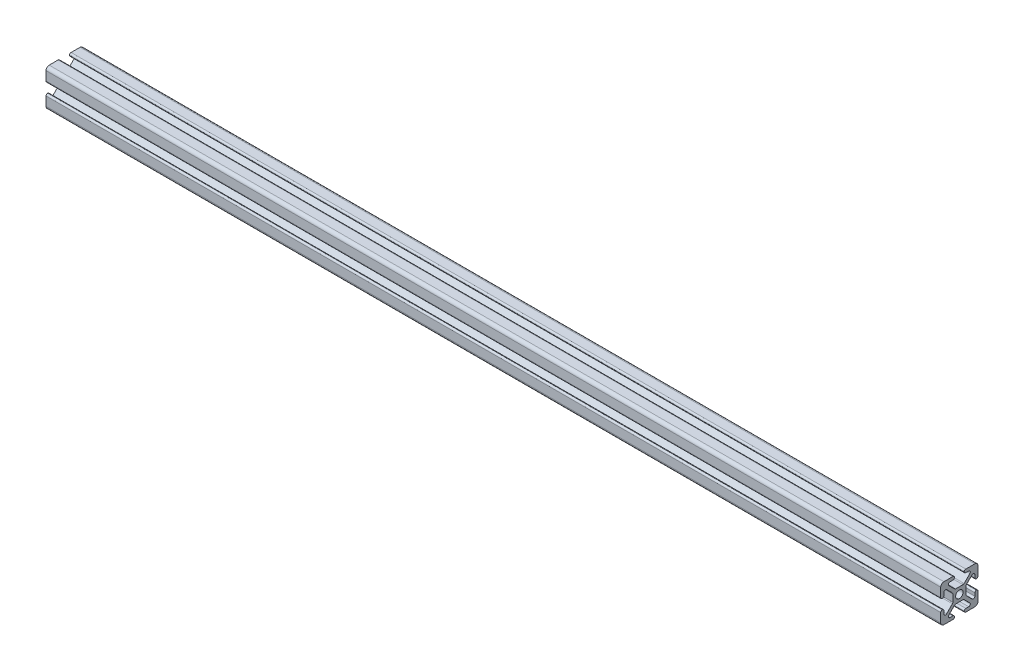
SolidWorks part; units mm, degrees
ref_plane "Front Plane" through (0, 0, 0) normal (1, 0, 0) x (0, 1, 0)
ref_plane "Top Plane" through (0, 0, 0) normal (0, 0, 1) x (0, 1, 0)
ref_plane "Right Plane" through (0, 0, 0) normal (0, 1, 0) x (-1, 0, 0)
sketch "Sketch1" plane through (0, 0, 0) normal (1, 0, 0) x (0, 1, 0)
  line L0 (0, 0) -> (0, 12.5) construction
  line L1 (-12.5, -12.5) -> (12.5, -12.5)
  line L2 (-12.5, -12.5) -> (-12.5, 12.5)
  line L3 (-12.5, 12.5) -> (12.5, 12.5)
  line L4 (12.5, -12.5) -> (12.5, 12.5)
  line L5 (-12.5, -12.5) -> (12.5, 12.5) construction
  line L6 (-12.5, 12.5) -> (12.5, -12.5) construction
  line L7 (-3.25, 12.5) -> (-3.25, 10.37)
  line L8 (-3.25, 10.37) -> (-8.8639, 10.37)
  line L9 (-8.8639, 10.37) -> (-2.8739, 4.38)
  line L10 (-2.8739, 4.38) -> (2.8739, 4.38)
  line L11 (8.8639, 10.37) -> (2.8739, 4.38)
  line L12 (3.25, 10.37) -> (8.8639, 10.37)
  line L13 (3.25, 12.5) -> (3.25, 10.37)
  line L14 (12.5, -3.25) -> (10.37, -3.25)
  line L15 (10.37, -3.25) -> (10.37, -8.8639)
  line L16 (10.37, -8.8639) -> (4.38, -2.8739)
  line L17 (4.38, 2.8739) -> (4.38, -2.8739)
  line L18 (10.37, 8.8639) -> (4.38, 2.8739)
  line L19 (10.37, 3.25) -> (10.37, 8.8639)
  line L20 (12.5, 3.25) -> (10.37, 3.25)
  line L21 (-3.25, -12.5) -> (-3.25, -10.37)
  line L22 (-3.25, -10.37) -> (-8.8639, -10.37)
  line L23 (-8.8639, -10.37) -> (-2.8739, -4.38)
  line L24 (2.8739, -4.38) -> (-2.8739, -4.38)
  line L25 (8.8639, -10.37) -> (2.8739, -4.38)
  line L26 (3.25, -10.37) -> (8.8639, -10.37)
  line L27 (3.25, -12.5) -> (3.25, -10.37)
  line L28 (-12.5, 3.25) -> (-10.37, 3.25)
  line L29 (-10.37, 3.25) -> (-10.37, 8.8639)
  line L30 (-10.37, 8.8639) -> (-4.38, 2.8739)
  line L31 (-4.38, -2.8739) -> (-4.38, 2.8739)
  line L32 (-10.37, -8.8639) -> (-4.38, -2.8739)
  line L33 (-10.37, -3.25) -> (-10.37, -8.8639)
  line L34 (-12.5, -3.25) -> (-10.37, -3.25)
  circle A0 centre (0, 0) radius 2.5
  point P0 (0, 0)
  point P15 (0, 4.38)
  dimension "D3" = 5
  dimension "D1" = 25
  dimension "D2" = 25
  dimension "D4" = 2.13
  dimension "D5" = 2.13
  dimension "D6" = 6.5
  dimension "D7" = 4.38
  dimension "D8" = 4
extrude "Boss-Extrude1" add sketch "Sketch1" along normal blind 600 contours L34 L2 L1 L21 L22 L23 L24 L25 L26 L27 L4 L14 L15 L16 L17 L18 L19 L20 L3 L13 L12 L11 L10 L9 L8 L7 L28 L29 L30 L31 L32 L33 A0 region at (0, -12.1464, -7.875)
fillet "Fillet1" radius 1.065 32 edges at (300, -10.37, -8.8639) (300, 2.8739, -4.38) (300, -2.8739, -4.38) (300, -4.38, 2.8739) (300, -4.38, -2.8739) (300, -2.8739, 4.38) (300, 2.8739, 4.38) (300, 4.38, 2.8739) (300, 4.38, -2.8739) (300, -8.8639, -10.37) (300, 8.8639, -10.37) (300, 10.37, -8.8639) (300, -10.37, 8.8639) (300, -8.8639, 10.37) (300, 10.37, 8.8639) (300, 8.8639, 10.37) (300, 12.5, 3.25) (300, -3.25, -12.5) (300, -10.37, 3.25) (300, 10.37, 3.25) (300, -10.37, -3.25) (300, -12.5, -3.25) (300, -12.5, 3.25) (300, 3.25, -10.37) (300, -3.25, -10.37) (300, 3.25, -12.5) (300, 10.37, -3.25) (300, 12.5, -3.25) (300, 3.25, 12.5) (300, 3.25, 10.37) (300, -3.25, 10.37) (300, -3.25, 12.5)
fillet "Fillet2" radius 2.13 4 edges at (300, 12.5, -12.5) (300, -12.5, -12.5) (300, 12.5, 12.5) (300, -12.5, 12.5)
sketch "Sketch2" plane through (600, 0, 0) normal (1, 0, 0) x (0, 1, 0)
  line L0 (10.37, -12.5) -> (4.315, -12.5)
  line L1 (10.37, -12.5) -> (4.315, -12.5)
  line L2 (4.315, -10.37) -> (6.2927, -10.37)
  line L3 (4.315, -10.37) -> (6.2927, -10.37)
  line L4 (7.0458, -8.5519) -> (3.1858, -4.6919)
  line L5 (7.0458, -8.5519) -> (3.1858, -4.6919)
  line L6 (2.4327, -4.38) -> (-2.4327, -4.38)
  line L7 (2.4327, -4.38) -> (-2.4327, -4.38)
  line L8 (-3.1858, -4.6919) -> (-7.0458, -8.5519)
  line L9 (-3.1858, -4.6919) -> (-7.0458, -8.5519)
  line L10 (-6.2927, -10.37) -> (-4.315, -10.37)
  line L11 (-6.2927, -10.37) -> (-4.315, -10.37)
  line L12 (-4.315, -12.5) -> (-10.37, -12.5)
  line L13 (-4.315, -12.5) -> (-10.37, -12.5)
  line L14 (-12.5, -10.37) -> (-12.5, -4.315)
  line L15 (-12.5, -10.37) -> (-12.5, -4.315)
  line L16 (-10.37, -4.315) -> (-10.37, -6.2927)
  line L17 (-10.37, -4.315) -> (-10.37, -6.2927)
  line L18 (-8.5519, -7.0458) -> (-4.6919, -3.1858)
  line L19 (-8.5519, -7.0458) -> (-4.6919, -3.1858)
  line L20 (-4.38, -2.4327) -> (-4.38, 2.4327)
  line L21 (-4.38, -2.4327) -> (-4.38, 2.4327)
  line L22 (-4.6919, 3.1858) -> (-8.5519, 7.0458)
  line L23 (-4.6919, 3.1858) -> (-8.5519, 7.0458)
  line L24 (-10.37, 6.2927) -> (-10.37, 4.315)
  line L25 (-10.37, 6.2927) -> (-10.37, 4.315)
  line L26 (-12.5, 4.315) -> (-12.5, 10.37)
  line L27 (-12.5, 4.315) -> (-12.5, 10.37)
  line L28 (-10.37, 12.5) -> (-4.315, 12.5)
  line L29 (-10.37, 12.5) -> (-4.315, 12.5)
  line L30 (-4.315, 10.37) -> (-6.2927, 10.37)
  line L31 (-4.315, 10.37) -> (-6.2927, 10.37)
  line L32 (-7.0458, 8.5519) -> (-3.1858, 4.6919)
  line L33 (-7.0458, 8.5519) -> (-3.1858, 4.6919)
  line L34 (-2.4327, 4.38) -> (2.4327, 4.38)
  line L35 (-2.4327, 4.38) -> (2.4327, 4.38)
  line L36 (3.1858, 4.6919) -> (7.0458, 8.5519)
  line L37 (3.1858, 4.6919) -> (7.0458, 8.5519)
  line L38 (6.2927, 10.37) -> (4.315, 10.37)
  line L39 (6.2927, 10.37) -> (4.315, 10.37)
  line L40 (4.315, 12.5) -> (10.37, 12.5)
  line L41 (4.315, 12.5) -> (10.37, 12.5)
  line L42 (12.5, 10.37) -> (12.5, 4.315)
  line L43 (12.5, 10.37) -> (12.5, 4.315)
  line L44 (10.37, 4.315) -> (10.37, 6.2927)
  line L45 (10.37, 4.315) -> (10.37, 6.2927)
  line L46 (8.5519, 7.0458) -> (4.6919, 3.1858)
  line L47 (8.5519, 7.0458) -> (4.6919, 3.1858)
  line L48 (4.38, 2.4327) -> (4.38, -2.4327)
  line L49 (4.38, 2.4327) -> (4.38, -2.4327)
  line L50 (4.6919, -3.1858) -> (8.5519, -7.0458)
  line L51 (4.6919, -3.1858) -> (8.5519, -7.0458)
  line L52 (10.37, -6.2927) -> (10.37, -4.315)
  line L53 (10.37, -6.2927) -> (10.37, -4.315)
  line L54 (12.5, -4.315) -> (12.5, -10.37)
  line L55 (12.5, -4.315) -> (12.5, -10.37)
  arc A0 (10.37, -12.5) -> (12.5, -10.37) centre (10.37, -10.37) ccw
  circle A1 centre (0, 0) radius 2.5
  circle A2 centre (0, 0) radius 2.5
  arc A3 (10.37, -12.5) -> (12.5, -10.37) centre (10.37, -10.37) ccw
  arc A4 (3.25, -11.435) -> (4.315, -12.5) centre (4.315, -11.435) ccw
  arc A5 (3.25, -11.435) -> (4.315, -12.5) centre (4.315, -11.435) ccw
  arc A6 (4.315, -10.37) -> (3.25, -11.435) centre (4.315, -11.435) ccw
  arc A7 (4.315, -10.37) -> (3.25, -11.435) centre (4.315, -11.435) ccw
  arc A8 (6.2927, -10.37) -> (7.0458, -8.5519) centre (6.2927, -9.305) ccw
  arc A9 (6.2927, -10.37) -> (7.0458, -8.5519) centre (6.2927, -9.305) ccw
  arc A10 (3.1858, -4.6919) -> (2.4327, -4.38) centre (2.4327, -5.445) ccw
  arc A11 (3.1858, -4.6919) -> (2.4327, -4.38) centre (2.4327, -5.445) ccw
  arc A12 (-2.4327, -4.38) -> (-3.1858, -4.6919) centre (-2.4327, -5.445) ccw
  arc A13 (-2.4327, -4.38) -> (-3.1858, -4.6919) centre (-2.4327, -5.445) ccw
  arc A14 (-7.0458, -8.5519) -> (-6.2927, -10.37) centre (-6.2927, -9.305) ccw
  arc A15 (-7.0458, -8.5519) -> (-6.2927, -10.37) centre (-6.2927, -9.305) ccw
  arc A16 (-3.25, -11.435) -> (-4.315, -10.37) centre (-4.315, -11.435) ccw
  arc A17 (-3.25, -11.435) -> (-4.315, -10.37) centre (-4.315, -11.435) ccw
  arc A18 (-4.315, -12.5) -> (-3.25, -11.435) centre (-4.315, -11.435) ccw
  arc A19 (-4.315, -12.5) -> (-3.25, -11.435) centre (-4.315, -11.435) ccw
  arc A20 (-12.5, -10.37) -> (-10.37, -12.5) centre (-10.37, -10.37) ccw
  arc A21 (-12.5, -10.37) -> (-10.37, -12.5) centre (-10.37, -10.37) ccw
  arc A22 (-11.435, -3.25) -> (-12.5, -4.315) centre (-11.435, -4.315) ccw
  arc A23 (-11.435, -3.25) -> (-12.5, -4.315) centre (-11.435, -4.315) ccw
  arc A24 (-10.37, -4.315) -> (-11.435, -3.25) centre (-11.435, -4.315) ccw
  arc A25 (-10.37, -4.315) -> (-11.435, -3.25) centre (-11.435, -4.315) ccw
  arc A26 (-10.37, -6.2927) -> (-8.5519, -7.0458) centre (-9.305, -6.2927) ccw
  arc A27 (-10.37, -6.2927) -> (-8.5519, -7.0458) centre (-9.305, -6.2927) ccw
  arc A28 (-4.6919, -3.1858) -> (-4.38, -2.4327) centre (-5.445, -2.4327) ccw
  arc A29 (-4.6919, -3.1858) -> (-4.38, -2.4327) centre (-5.445, -2.4327) ccw
  arc A30 (-4.38, 2.4327) -> (-4.6919, 3.1858) centre (-5.445, 2.4327) ccw
  arc A31 (-4.38, 2.4327) -> (-4.6919, 3.1858) centre (-5.445, 2.4327) ccw
  arc A32 (-8.5519, 7.0458) -> (-10.37, 6.2927) centre (-9.305, 6.2927) ccw
  arc A33 (-8.5519, 7.0458) -> (-10.37, 6.2927) centre (-9.305, 6.2927) ccw
  arc A34 (-11.435, 3.25) -> (-10.37, 4.315) centre (-11.435, 4.315) ccw
  arc A35 (-11.435, 3.25) -> (-10.37, 4.315) centre (-11.435, 4.315) ccw
  arc A36 (-12.5, 4.315) -> (-11.435, 3.25) centre (-11.435, 4.315) ccw
  arc A37 (-12.5, 4.315) -> (-11.435, 3.25) centre (-11.435, 4.315) ccw
  arc A38 (-10.37, 12.5) -> (-12.5, 10.37) centre (-10.37, 10.37) ccw
  arc A39 (-10.37, 12.5) -> (-12.5, 10.37) centre (-10.37, 10.37) ccw
  arc A40 (-3.25, 11.435) -> (-4.315, 12.5) centre (-4.315, 11.435) ccw
  arc A41 (-3.25, 11.435) -> (-4.315, 12.5) centre (-4.315, 11.435) ccw
  arc A42 (-4.315, 10.37) -> (-3.25, 11.435) centre (-4.315, 11.435) ccw
  arc A43 (-4.315, 10.37) -> (-3.25, 11.435) centre (-4.315, 11.435) ccw
  arc A44 (-6.2927, 10.37) -> (-7.0458, 8.5519) centre (-6.2927, 9.305) ccw
  arc A45 (-6.2927, 10.37) -> (-7.0458, 8.5519) centre (-6.2927, 9.305) ccw
  arc A46 (-3.1858, 4.6919) -> (-2.4327, 4.38) centre (-2.4327, 5.445) ccw
  arc A47 (-3.1858, 4.6919) -> (-2.4327, 4.38) centre (-2.4327, 5.445) ccw
  arc A48 (2.4327, 4.38) -> (3.1858, 4.6919) centre (2.4327, 5.445) ccw
  arc A49 (2.4327, 4.38) -> (3.1858, 4.6919) centre (2.4327, 5.445) ccw
  arc A50 (7.0458, 8.5519) -> (6.2927, 10.37) centre (6.2927, 9.305) ccw
  arc A51 (7.0458, 8.5519) -> (6.2927, 10.37) centre (6.2927, 9.305) ccw
  arc A52 (3.25, 11.435) -> (4.315, 10.37) centre (4.315, 11.435) ccw
  arc A53 (3.25, 11.435) -> (4.315, 10.37) centre (4.315, 11.435) ccw
  arc A54 (4.315, 12.5) -> (3.25, 11.435) centre (4.315, 11.435) ccw
  arc A55 (4.315, 12.5) -> (3.25, 11.435) centre (4.315, 11.435) ccw
  arc A56 (12.5, 10.37) -> (10.37, 12.5) centre (10.37, 10.37) ccw
  arc A57 (12.5, 10.37) -> (10.37, 12.5) centre (10.37, 10.37) ccw
  arc A58 (11.435, 3.25) -> (12.5, 4.315) centre (11.435, 4.315) ccw
  arc A59 (11.435, 3.25) -> (12.5, 4.315) centre (11.435, 4.315) ccw
  arc A60 (10.37, 4.315) -> (11.435, 3.25) centre (11.435, 4.315) ccw
  arc A61 (10.37, 4.315) -> (11.435, 3.25) centre (11.435, 4.315) ccw
  arc A62 (10.37, 6.2927) -> (8.5519, 7.0458) centre (9.305, 6.2927) ccw
  arc A63 (10.37, 6.2927) -> (8.5519, 7.0458) centre (9.305, 6.2927) ccw
  arc A64 (4.6919, 3.1858) -> (4.38, 2.4327) centre (5.445, 2.4327) ccw
  arc A65 (4.6919, 3.1858) -> (4.38, 2.4327) centre (5.445, 2.4327) ccw
  arc A66 (4.38, -2.4327) -> (4.6919, -3.1858) centre (5.445, -2.4327) ccw
  arc A67 (4.38, -2.4327) -> (4.6919, -3.1858) centre (5.445, -2.4327) ccw
  arc A68 (8.5519, -7.0458) -> (10.37, -6.2927) centre (9.305, -6.2927) ccw
  arc A69 (8.5519, -7.0458) -> (10.37, -6.2927) centre (9.305, -6.2927) ccw
  arc A70 (11.435, -3.25) -> (10.37, -4.315) centre (11.435, -4.315) ccw
  arc A71 (11.435, -3.25) -> (10.37, -4.315) centre (11.435, -4.315) ccw
  arc A72 (12.5, -4.315) -> (11.435, -3.25) centre (11.435, -4.315) ccw
  arc A73 (12.5, -4.315) -> (11.435, -3.25) centre (11.435, -4.315) ccw
  dimension "D1" = 0
